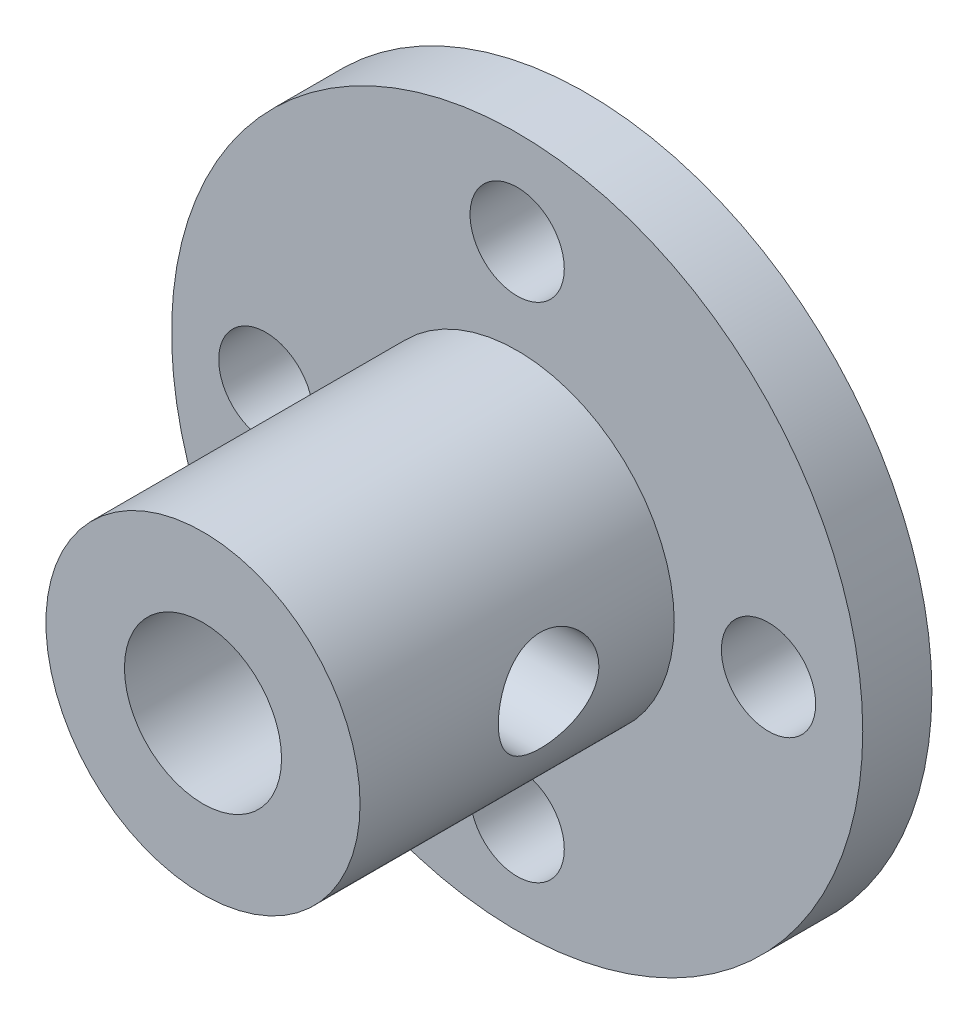
SolidWorks part; units mm, degrees
material "1.6657 (14NiCrMo13-4)"
ref_plane "前视基准面" through (0, 0, 0) normal (0, 0, 1) x (1, 0, 0)
ref_plane "上视基准面" through (0, 0, 0) normal (0, 1, 0) x (1, 0, 0)
ref_plane "右视基准面" through (0, 0, 0) normal (1, 0, 0) x (0, 0, -1)
sketch "草图1" plane through (0, 0, 0) normal (0, 0, 1) x (1, 0, 0)
  circle A0 centre (0, 0) radius 11
  dimension "D1" = 22
extrude "凸台-拉伸1" add sketch "草图1" along normal blind 2.2
sketch "草图2" plane through (0, 0, 2.2) normal (0, 0, 1) x (1, 0, 0)
  circle A0 centre (0, 0) radius 5
  dimension "D1" = 10
extrude "凸台-拉伸2" add sketch "草图2" along normal blind 10
sketch "草图3" plane through (0, 0, 2.2) normal (0, 0, 1) x (1, 0, 0)
  line L0 (0, 0) -> (8, 0) construction
  circle A0 centre (0, 0) radius 8 construction
  circle A1 centre (8, 0) radius 1.5
  circle A2 centre (0, -8) radius 1.5
  circle A3 centre (-8, 0) radius 1.5
  circle A4 centre (0, 8) radius 1.5
  point P14 (0, 0)
  dimension "D1" = 16
  dimension "D2" = 3
  dimension "D3" = 4
extrude "切除-拉伸1" cut sketch "草图3" against normal blind 10
sketch "草图4" plane through (0, 0, 0) normal (1, 0, 0) x (0, 0, -1)
  line L0 (-2.2, 11) -> (-2.2, -11) construction
  circle A0 centre (-6.2, 0) radius 1.6
  dimension "D2" = 3.2
  dimension "D1" = 4
extrude "切除-拉伸2" cut sketch "草图4" against normal blind 10 and the other way blind 10
sketch "草图5" plane through (0, 0, 0) normal (0, 0, -1) x (-1, 0, 0)
  circle A0 centre (0, 0) radius 2.5
  dimension "D1" = 5
extrude "切除-拉伸3" cut sketch "草图5" against normal blind 50
